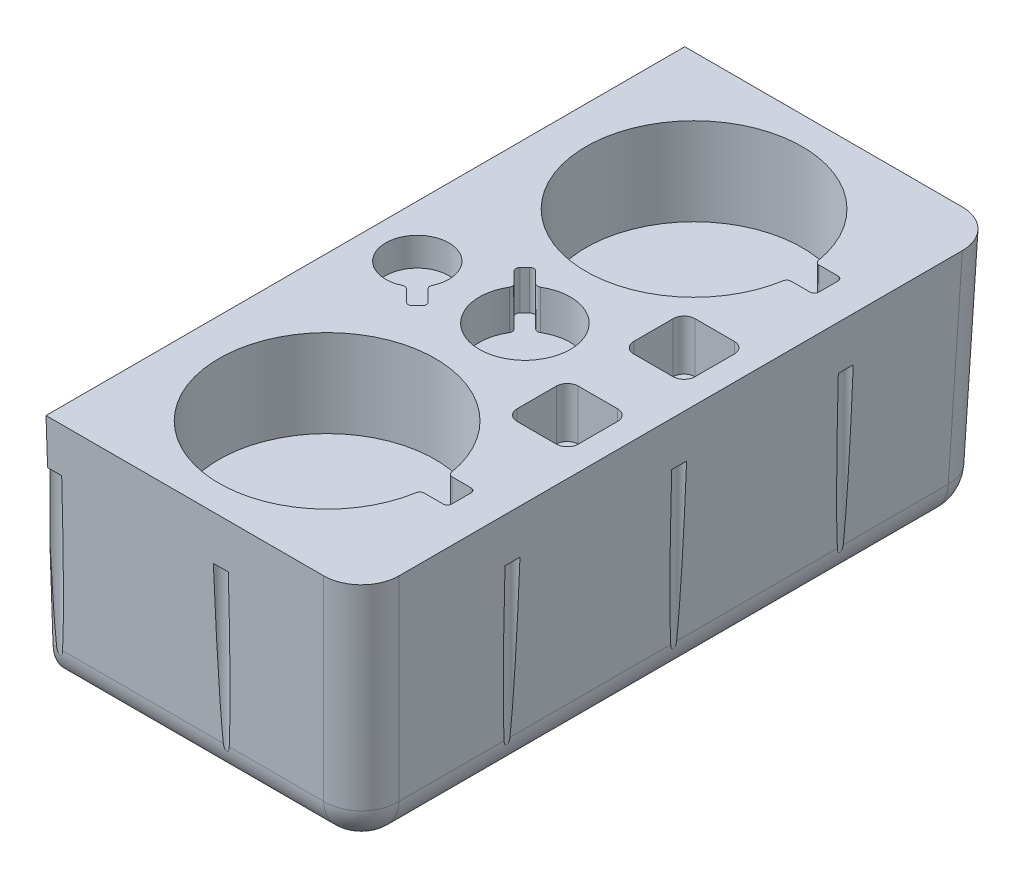
SolidWorks part; units mm, degrees
ref_plane "Front Plane" through (0, 0, 0) normal (0, 0, 1) x (1, 0, 0)
ref_plane "Top Plane" through (0, 0, 0) normal (0, 1, 0) x (1, 0, 0)
ref_plane "Right Plane" through (0, 0, 0) normal (1, 0, 0) x (0, 0, -1)
sketch "Sketch3" plane through (0, 0, 0) normal (0, 1, 0) x (1, 0, 0)
  line L1 (-70.2, -142.24) -> (70.2, -142.24)
  line L2 (-70.2, -142.24) -> (-70.2, 142.24)
  line L3 (-70.2, 142.24) -> (70.2, 142.24)
  line L4 (70.2, -142.24) -> (70.2, 142.24)
  line L5 (-70.2, -142.24) -> (70.2, 142.24) construction
  line L6 (-70.2, 142.24) -> (70.2, -142.24) construction
  point P0 (0, 0)
  dimension "D1" = 140.4
  dimension "D2" = 284.48
extrude "Boss-Extrude1" add sketch "Sketch3" along normal blind 109.22 draft 2 draft outward yes
sketch "Sketch1" plane through (0, 0, 0) normal (0, 1, 0) x (1, 0, 0)
  line L0 (45.236, 90.304) -> (57.636, 90.304)
  line L5 (57.636, 90.304) -> (57.636, 77.504)
  line L6 (57.636, 77.504) -> (45.236, 77.504)
  line L7 (45.236, -77.504) -> (57.636, -77.504)
  line L8 (57.636, -77.504) -> (57.636, -90.304)
  line L9 (57.636, -90.304) -> (45.236, -90.304)
  line L16 (39.838, 12.7) -> (57.838, 12.7)
  line L17 (34.838, 17.7) -> (34.838, 35.7)
  line L18 (39.838, 40.7) -> (57.838, 40.7)
  line L19 (62.838, 17.7) -> (62.838, 35.7)
  line L20 (34.838, 12.7) -> (62.838, 40.7) construction
  line L21 (34.838, 40.7) -> (62.838, 12.7) construction
  line L22 (39.838, -40.7) -> (57.838, -40.7)
  line L23 (34.838, -35.7) -> (34.838, -17.7)
  line L24 (39.838, -12.7) -> (57.838, -12.7)
  line L25 (62.838, -35.7) -> (62.838, -17.7)
  line L26 (34.838, -40.7) -> (62.838, -12.7) construction
  line L27 (34.838, -12.7) -> (62.838, -40.7) construction
  line L28 (-72.9829, 0) -> (78.453, 0) construction
  line L29 (74.014, 146.054) -> (-74.014, 146.054) construction
  line L31 (-74.014, 146.054) -> (-74.014, -146.054) construction
  line L34 (74.014, -146.054) -> (74.014, 146.054) construction
  line L35 (-74.014, -146.054) -> (74.014, -146.054) construction
  line L42 (-16.8542, 24.539) -> (-9.2882, 16.973)
  line L43 (-16.8542, 24.539) -> (-21.804, 19.5893)
  line L44 (-21.804, 19.5893) -> (-14.2379, 12.0232)
  line L45 (-19.3291, 22.0641) -> (2.735, 0) construction
  line L46 (-46.4604, 0) -> (-28.7687, -17.6916) construction
  line L47 (-39.0218, -12.3883) -> (-31.2436, -20.1665)
  line L48 (-31.2436, -20.1665) -> (-26.2939, -15.2167)
  line L49 (-26.2939, -15.2167) -> (-34.072, -7.4386)
  arc A0 (45.236, 90.304) -> (45.236, 77.504) centre (-3.798, 83.904) ccw
  arc A1 (45.236, -77.504) -> (45.236, -90.304) centre (-3.798, -83.904) ccw
  arc A4 (57.838, 40.7) -> (62.838, 35.7) centre (57.838, 35.7) cw
  arc A5 (57.838, 12.7) -> (62.838, 17.7) centre (57.838, 17.7) ccw
  arc A6 (39.838, 12.7) -> (34.838, 17.7) centre (39.838, 17.7) cw
  arc A7 (34.838, 35.7) -> (39.838, 40.7) centre (39.838, 35.7) cw
  arc A8 (39.838, -40.7) -> (34.838, -35.7) centre (39.838, -35.7) cw
  arc A9 (57.838, -40.7) -> (62.838, -35.7) centre (57.838, -35.7) ccw
  arc A10 (57.838, -12.7) -> (62.838, -17.7) centre (57.838, -17.7) cw
  arc A11 (34.838, -17.7) -> (39.838, -12.7) centre (39.838, -17.7) cw
  arc A12 (-34.072, -7.4386) -> (-39.0218, -12.3883) centre (-46.4604, 0) ccw
  arc A16 (-14.2379, 12.0232) -> (-9.2882, 16.973) centre (2.735, 0) ccw
  circle A17 centre (48.838, 26.7) radius 8.35
  circle A18 centre (48.838, -26.7) radius 8.35
  point P13 (48.838, 12.7)
  point P25 (48.838, 26.7)
  point P42 (48.838, -26.7)
  dimension "D3" = 98.9
  dimension "D4" = 98.9
  dimension "D8" = 20.8
  dimension "D11" = 11.303
  dimension "D15" = 5
  dimension "D18" = 5
  dimension "D5" = 12.7
  dimension "D19" = 77.8121
  dimension "D20" = 12.7
  dimension "D21" = 28.9
  dimension "D22" = 135
  dimension "D23" = 7
  dimension "D25" = 12.7
  dimension "D12" = 13.1037
  dimension "D13" = 45
  dimension "D27" = 16.7
  dimension "D1" = 12.4
  dimension "D2" = 12.8
  dimension "D6" = 12.8
  dimension "D7" = 12.4
  dimension "D9" = 7
  dimension "D10" = 10.7
  dimension "D14" = 28
  dimension "D16" = 28
  dimension "D17" = 28
  dimension "D24" = 11
  dimension "D26" = 11.176
fillet "Fillet1" radius 17.272 5 edges at (0, 0, -142.24) (0, 0, 142.24) (70.2, 0, 0) (72.107, 54.61, -144.147) (72.107, 54.61, 144.147)
extrude "Cut-Extrude1" cut sketch "Sketch1" against normal blind 40 from surface contours A0 L6 L5 L0 | A1 L9 L8 L7 starting at face at (20.1096, 109.22, 0)
extrude "Cut-Extrude2" cut sketch "Sketch1<4>" against normal blind 13 from surface contours L49 A12 L47 L48 region at (-45.034, 0, 1.4263) starting at face at (26.815, 109.22, 83.904)
sketch "Sketch1<4>" plane through (0, 0, 0) normal (0, 1, 0) x (1, 0, 0) same geometry as "Sketch1"
extrude "Cut-Extrude3" cut sketch "Sketch1<5>" against normal blind 18 from surface contours L44 A16 L42 L43 region at (1.7934, 0, -0.9416) starting at face at (-37.6906, 109.22, 8.7697)
sketch "Sketch1<5>" plane through (0, 0, 0) normal (0, 1, 0) x (1, 0, 0) same geometry as "Sketch1"
extrude "Cut-Extrude5" cut sketch "Sketch1<6>" against normal blind 23 from surface contours A7 L17 A6 L16 A5 L19 A4 L18 | A11 L23 A8 L22 A9 L25 A10 L24 region at (36.5825, 0, -14.4445) region at (36.5825, 0, 38.9555) starting at face at (-8.2446, 109.22, -10.9796)
sketch "Sketch1<6>" plane through (0, 0, 0) normal (0, 1, 0) x (1, 0, 0) same geometry as "Sketch1"
extrude "Cut-Extrude7" cut sketch "Sketch1<7>" against normal blind 31 from surface contours A17 | A18 region at (48.838, 0, -26.7) region at (48.838, 0, 26.7) starting at face at (48.838, 109.22, 26.7)
sketch "Sketch1<7>" plane through (0, 0, 0) normal (0, 1, 0) x (1, 0, 0) same geometry as "Sketch1"
fillet "Fillet2" radius 2 16 edges at (45.236, 89.22, 90.304) (45.236, 89.22, 77.504) (57.636, 89.22, 77.504) (57.636, 89.22, 90.304) (-31.2436, 102.72, 20.1665) (-26.2939, 102.72, 15.2167) (-34.072, 102.72, 7.4386) (-39.0218, 102.72, 12.3883) (-14.2379, 100.22, -12.0232) (-21.804, 100.22, -19.5893) (-16.8542, 100.22, -24.539) (-9.2882, 100.22, -16.973) (45.236, 89.22, -77.504) (57.636, 89.22, -90.304) (57.636, 89.22, -77.504) (45.236, 89.22, -90.304)
sketch "Sketch4" plane through (0, 0, 0) normal (0, 0, 1) x (1, 0, 0)
  line L1 (-74.014, 109.22) -> (56.7526, 109.22) construction
  line L2 (-70.2, 109.22) -> (-70.2, 0)
  line L3 (-70.2, 0) -> (-85.4637, 109.22)
  line L4 (-85.4637, 109.22) -> (-70.2, 109.22)
  dimension "D2" = 110.2814
extrude "Cut-Extrude8" cut sketch "Sketch4" against normal through all both and the other way through all contours L3 L4 L2
ref_plane "Plane1" through (0, 88.22, 0) normal (0, 1, 0) x (1, 0, 0)
sketch "Sketch6" plane through (0, 88.22, 0) normal (0, 1, 0) x (1, 0, 0)
  line L0 (74.014, -128.7926) -> (74.014, 128.7926) construction
  line L1 (74.014, 3.5) -> (74.014, -3.5)
  line L2 (74.014, 79.7) -> (74.014, 72.7)
  line L3 (-9.7237, 0) -> (10.798, 0) construction
  line L4 (74.014, -79.7) -> (74.014, -72.7)
  line L5 (56.7526, 146.054) -> (-70.2, 146.054) construction
  line L6 (5.514, 146.054) -> (12.514, 146.054)
  line L7 (-70.686, 146.054) -> (-63.686, 146.054)
  line L8 (-70.686, -146.054) -> (-63.686, -146.054)
  line L9 (5.514, -146.054) -> (12.514, -146.054)
  arc A0 (74.014, 3.5) -> (74.014, -3.5) centre (74.014, 0) ccw
  arc A1 (74.014, 79.7) -> (74.014, 72.7) centre (74.014, 76.2) ccw
  arc A2 (74.014, -79.7) -> (74.014, -72.7) centre (74.014, -76.2) cw
  arc A3 (5.514, 146.054) -> (12.514, 146.054) centre (9.014, 146.054) ccw
  arc A4 (-70.686, 146.054) -> (-63.686, 146.054) centre (-67.186, 146.054) ccw
  arc A5 (-70.686, -146.054) -> (-63.686, -146.054) centre (-67.186, -146.054) cw
  arc A6 (5.514, -146.054) -> (12.514, -146.054) centre (9.014, -146.054) cw
  dimension "D1" = 7
  dimension "D2" = 76.2
  dimension "D3" = 65
  dimension "D4" = 76.2
extrude "Cut-Extrude9" cut sketch "Sketch6" against normal up to next
